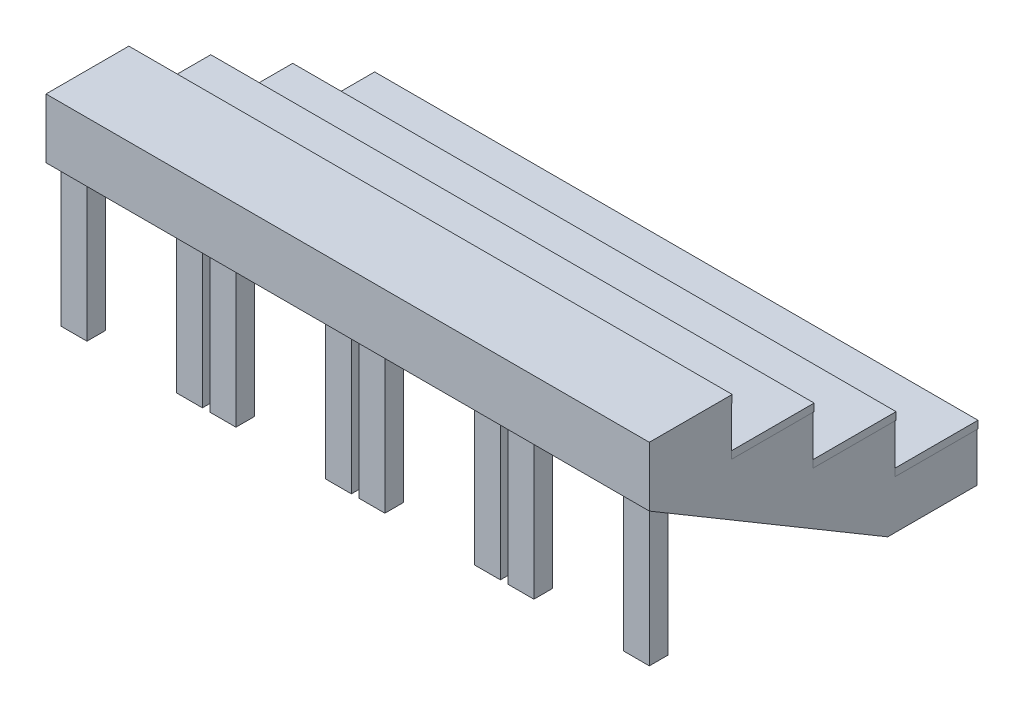
SolidWorks part; units mm, degrees
material "Cedar"
ref_plane "Front" through (0, 0, 0) normal (0, 0, 1) x (1, 0, 0)
ref_plane "Top" through (0, 0, 0) normal (0, 1, 0) x (1, 0, 0)
ref_plane "Right" through (0, 0, 0) normal (1, 0, 0) x (0, 0, -1)
sketch "Sketch1" plane through (0, 0, 0) normal (1, 0, 0) x (0, 0, -1)
  line L0 (0, 0) -> (0, 165.1)
  line L1 (0, 165.1) -> (-279.4, 165.1)
  line L2 (-279.4, 165.1) -> (-279.4, 330.2)
  line L3 (-279.4, 330.2) -> (-558.8, 330.2)
  line L4 (-558.8, 330.2) -> (-558.8, 495.3)
  line L5 (-558.8, 495.3) -> (-838.2, 495.3)
  line L6 (-838.2, 495.3) -> (-838.2, 660.4)
  line L7 (-838.2, 660.4) -> (-1117.6, 660.4)
  line L8 (-1117.6, 660.4) -> (-1117.6, 482.6)
  line L9 (-1117.6, 482.6) -> (-304.8, 0)
  line L10 (-304.8, 0) -> (0, 0)
  dimension "D1" = 165.1
  dimension "D2" = 279.4
  dimension "D3" = 304.8
  dimension "D4" = 177.8
extrude "Boss-Extrude1" add sketch "Sketch1" along normal blind 25.4
pattern_linear "LPattern1" count 5 spacing 508 along (1, 0, 0) of bodies 179
sketch "Sketch2" plane through (2057.4, 0, 0) normal (1, 0, 0) x (0, 0, -1)
  line L1 (-279.4, 165.1) -> (3.175, 165.1)
  line L2 (-279.4, 165.1) -> (-279.4, 190.5)
  line L3 (-279.4, 190.5) -> (3.175, 190.5)
  line L4 (3.175, 165.1) -> (3.175, 190.5)
  line L5 (-558.8, 330.2) -> (-276.225, 330.2)
  line L6 (-558.8, 330.2) -> (-558.8, 355.6)
  line L7 (-558.8, 355.6) -> (-276.225, 355.6)
  line L8 (-276.225, 330.2) -> (-276.225, 355.6)
  line L9 (-838.2, 495.3) -> (-555.625, 495.3)
  line L10 (-838.2, 495.3) -> (-838.2, 520.7)
  line L11 (-838.2, 520.7) -> (-555.625, 520.7)
  line L12 (-555.625, 495.3) -> (-555.625, 520.7)
  line L13 (-1117.6, 660.4) -> (-835.025, 660.4)
  line L14 (-1117.6, 660.4) -> (-1117.6, 685.8)
  line L15 (-1117.6, 685.8) -> (-835.025, 685.8)
  line L16 (-835.025, 660.4) -> (-835.025, 685.8)
  dimension "D1" = 282.575
  dimension "D2" = 25.4
extrude "Boss-Extrude2" add sketch "Sketch2" against normal up to surface (2057.4 mm away) separate body up to face at (0, 344.0545, 535.7091)
sketch "Sketch3" plane through (25.4, 0, 0) normal (1, 0, 0) x (0, 0, -1)
  line L1 (-1117.6, 660.4) -> (-1092.2, 660.4)
  line L2 (-1117.6, 660.4) -> (-1117.6, 482.6)
  line L3 (-1117.6, 482.6) -> (-1092.2, 482.6)
  line L4 (-1092.2, 660.4) -> (-1092.2, 482.6)
  dimension "D1" = 177.8
  dimension "D2" = 25.4
extrude "Boss-Extrude3" add sketch "Sketch3" along normal up to surface (2006.6 mm away) up to face at (2032, 344.0545, 535.7091)
sketch "Sketch5" plane through (0, 660.4, 0) normal (0, -1, 0) x (1, 0, 0)
  line L1 (25.4, 1092.2) -> (114.3, 1092.2)
  line L2 (25.4, 1092.2) -> (25.4, 1028.7)
  line L3 (25.4, 1028.7) -> (114.3, 1028.7)
  line L4 (114.3, 1092.2) -> (114.3, 1028.7)
  line L5 (508, 1092.2) -> (419.1, 1092.2)
  line L6 (508, 1092.2) -> (508, 1028.7)
  line L7 (508, 1028.7) -> (419.1, 1028.7)
  line L8 (419.1, 1092.2) -> (419.1, 1028.7)
  dimension "D1" = 88.9
  dimension "D2" = 63.5
  dimension "D3" = 88.9
  dimension "D4" = 63.5
extrude "Boss-Extrude4" add sketch "Sketch5" along normal up to surface (660.4 mm away) separate body up to face at (12.7, 0, 152.4)
pattern_linear "LPattern2" count 4 spacing 508 along (1, 0, 0) of bodies 189 190
